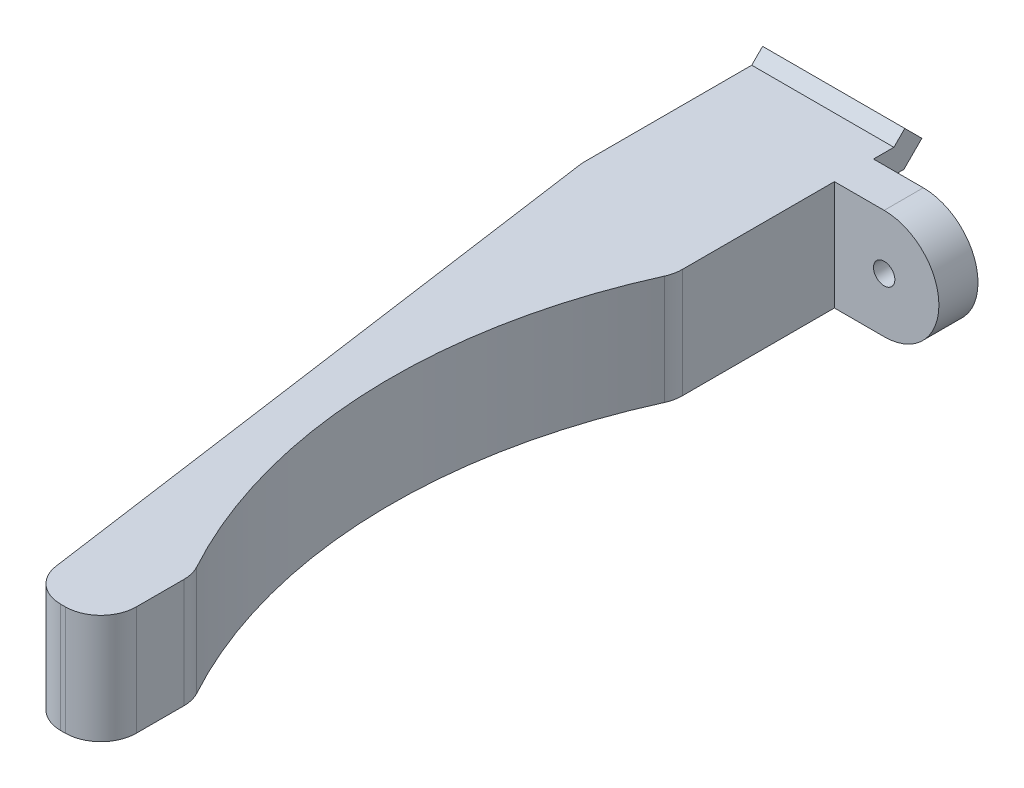
SolidWorks part; units mm, degrees
ref_plane "Front Plane" through (0, 0, 0) normal (0, 0, 1) x (1, 0, 0)
ref_plane "Top Plane" through (0, 0, 0) normal (0, 1, 0) x (1, 0, 0)
ref_plane "Right Plane" through (0, 0, 0) normal (1, 0, 0) x (0, 0, -1)
sketch "Sketch2" plane through (0, 0, 0) normal (0, 0, 1) x (1, 0, 0)
  line L0 (0, 5.9203) -> (0, 8.9503) construction
  line L1 (-5, -5.8182) -> (5, -5.8182)
  line L2 (-5, -5.8182) -> (-5, 8.9503)
  line L3 (-5, 8.9503) -> (5, 8.9503)
  line L4 (5, -5.8182) -> (5, 8.9503)
  line L5 (-5.0661, 8.9503) -> (32.6339, 8.9503) construction
  line L7 (26.9339, 5.9203) -> (-4.6913, 5.9203) construction
  line L8 (0, -5.8182) -> (0, -2.7882) construction
  point P0 (0, 0)
  dimension "D1" = 10
extrude "Boss-Extrude1" add sketch "Sketch2" along normal blind 5
sketch "Sketch8" plane through (-5, 0, 0) normal (-1, 0, 0) x (0, 0, 1)
  line L6 (-0.15, 5.7703) -> (0, 5.7703)
  line L7 (0, 8.9503) -> (0, -5.8182) construction
  line L8 (0, 5.7703) -> (0, 4.0703)
  line L9 (0, 4.0703) -> (-0.15, 4.0703)
  line L11 (-0.15, -1.9297) -> (0, -1.9297)
  line L12 (-2.1379, 4.0703) -> (-0.15, 4.0703)
  line L13 (-0.15, 4.0703) -> (-0.15, 5.7703)
  line L14 (-0.15, 5.7703) -> (-1.4337, 5.7703)
  line L15 (-1.4337, 5.7703) -> (-2.2, 6.5366)
  line L16 (-2.2, 6.5366) -> (-3.4021, 5.3345)
  line L17 (-3.4021, 5.3345) -> (-2.1379, 4.0703)
  line L18 (-2.1379, 4.0703) -> (-0.15, 4.0703)
  line L20 (-0.15, 5.7703) -> (-1.4337, 5.7703)
  line L21 (-1.4337, 5.7703) -> (-2.2, 6.5366)
  line L22 (-2.2, 6.5366) -> (-3.4021, 5.3345)
  line L23 (-3.4021, 5.3345) -> (-2.1379, 4.0703)
  line L24 (-2.1379, -1.9297) -> (-0.15, -1.9297)
  line L25 (-0.15, -1.9297) -> (-0.15, -0.2297)
  line L26 (-0.15, -0.2297) -> (-1.4337, -0.2297)
  line L27 (-1.4337, -0.2297) -> (-2.2, 0.5366)
  line L28 (-2.2, 0.5366) -> (-3.4021, -0.6655)
  line L29 (-3.4021, -0.6655) -> (-2.1379, -1.9297)
  line L30 (-2.1379, -1.9297) -> (-0.15, -1.9297)
  line L32 (-0.15, -0.2297) -> (-1.4337, -0.2297)
  line L33 (-1.4337, -0.2297) -> (-2.2, 0.5366)
  line L34 (-2.2, 0.5366) -> (-3.4021, -0.6655)
  line L35 (-3.4021, -0.6655) -> (-2.1379, -1.9297)
  line L37 (-0.15, -0.2297) -> (0, -0.2297)
  line L38 (0, -1.9297) -> (0, -0.2297)
  dimension "D1" = 0.15
  dimension "D2" = 0.15
extrude "Boss-Extrude4" add sketch "Sketch8" against normal up to surface (10 mm away) up to face at (5, 1.566, 2.5)
sketch "Sketch9" plane through (0, 0, 0) normal (0, 0, -1) x (-1, 0, 0)
  line L4 (-5, 8.9503) -> (-5, 5.7703)
  line L5 (-5, 5.7703) -> (5, 5.7703)
  line L6 (5, 5.7703) -> (5, 8.9503)
  line L7 (5, 8.9503) -> (-5, 8.9503)
  line L8 (-5, 8.9503) -> (-5, 5.7703)
  line L10 (5, 5.7703) -> (5, 8.9503)
  line L11 (5, 8.9503) -> (-5, 8.9503)
  line L16 (5, -1.9297) -> (-5, -1.9297)
  line L17 (-5, -1.9297) -> (-5, -5.8182)
  line L18 (-5, -5.8182) -> (5, -5.8182)
  line L19 (5, -5.8182) -> (5, -1.9297)
  line L21 (-5, -1.9297) -> (-5, -5.8182)
  line L22 (-5, -5.8182) -> (5, -5.8182)
  line L23 (5, -5.8182) -> (5, -1.9297)
  line L26 (-5, 5.7703) -> (5, 5.7703)
  line L27 (5, -1.9297) -> (-5, -1.9297)
  dimension "D1" = 0
  dimension "D2" = 0
extrude "Cut-Extrude3" cut sketch "Sketch9" against normal blind 5
sketch "Sketch10" plane through (0, 5.7703, 0) normal (0, 1, 0) x (1, 0, 0)
  line L0 (-5, -5) -> (-5, -10.5)
  line L1 (-5, -10.5) -> (1.3524, -55.7)
  line L2 (1.3524, -55.7) -> (6.3524, -55.7)
  line L3 (-5, -5) -> (5, -5)
  line L4 (-120.9789, 453.7107) -> (412.3545, 453.7107) construction
  line L5 (6.3524, -55.7) -> (6.3524, -49.2)
  line L6 (5, -5) -> (5, -14)
  arc A1 (5, -14) -> (6.3524, -49.2) centre (39.6089, -30.2962) ccw
  dimension "D1" = 172
  dimension "D2" = 45.2
  dimension "D3" = 5
  dimension "D4" = 6.5
  dimension "D5" = 5.5
  dimension "D6" = 9
extrude "Boss-Extrude5" add sketch "Sketch10" against normal up to surface (7.7 mm away) up to face at (0, -1.9297, 1.4311)
ref_plane "Plane1" through (0, 0, 2.75) normal (0, 0, 1) x (1, 0, 0)
sketch "Sketch12" plane through (0, 0, 0) normal (0, 0, 1) x (1, 0, 0)
  line L0 (5, 5.7703) -> (8.5, 5.7703)
  line L1 (8.5, -1.9297) -> (5, -1.9297)
  line L2 (5, -1.9297) -> (5, 5.7703)
  line L3 (1.3524, 5.7703) -> (6.3524, 5.7703) construction
  line L4 (1.3524, -1.9297) -> (6.3524, -1.9297) construction
  line L5 (5, 5.3345) -> (5, 6.5366) construction
  line L6 (6.3524, 5.7703) -> (1.3552, 5.7703) construction
  arc A0 (8.5, 5.7703) -> (8.5, -1.9297) centre (8.5, 1.9203) cw
  circle A1 centre (8.5, 1.9203) radius 0.75
  dimension "D1" = 1.5
  dimension "D2" = 3.5
extrude "Boss-Extrude7" add sketch "Sketch12" along normal up to surface (2.75 mm away) up to plane "Plane1"
fillet "Fillet1" radius 2.5 4 edges at (6.3524, 1.9203, 55.7) (1.3524, 1.9203, 55.7) (6.3524, 1.9203, 49.2) (5, 1.9203, 14)
